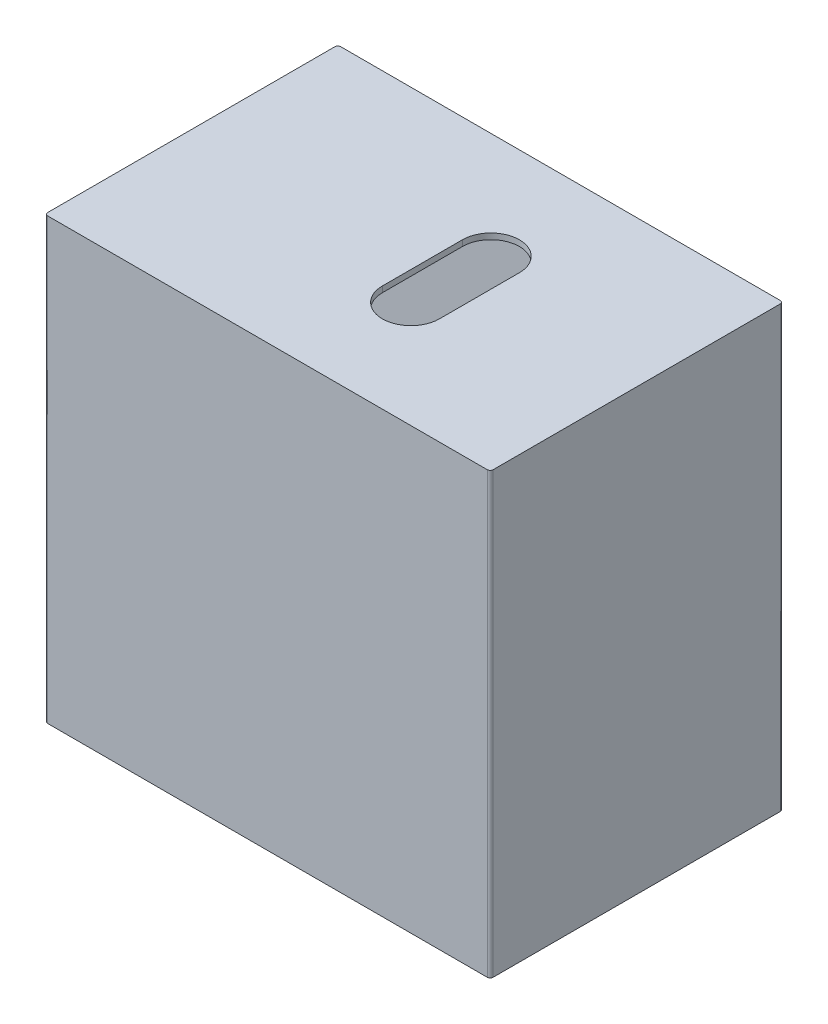
SolidWorks part; units mm, degrees
ref_plane "Front Plane" through (0, 0, 0) normal (0, 0, 1) x (1, 0, 0)
ref_plane "Top Plane" through (0, 0, 0) normal (0, 1, 0) x (1, 0, 0)
ref_plane "Right Plane" through (0, 0, 0) normal (1, 0, 0) x (0, 0, -1)
sketch "Sketch2" plane through (0, 0, 0) normal (0, 1, 0) x (1, 0, 0)
  line L0 (-14.8771, 11.2147) -> (17.0379, 11.2147)
  line L1 (17.0379, 11.2147) -> (17.0379, -11.4999)
  line L6 (17.0379, -11.4999) -> (-14.8548, -11.4999)
  line L7 (-19.8771, -6.4775) -> (-19.8771, 6.2147)
  line L8 (-29.1062, -20.0603) -> (-29.1062, 19.9397)
  line L9 (-75.1292, -50.0603) -> (74.8708, -50.0603)
  line L10 (-75.1292, 49.9397) -> (74.8708, 49.9397)
  line L11 (75.8708, 48.9397) -> (75.8708, -49.0603)
  line L12 (-29.1062, 19.9397) -> (-76.1292, 19.9397)
  line L13 (-29.1062, -20.0603) -> (-76.1292, -20.0603)
  line L14 (-76.1292, 48.9397) -> (-76.1292, 19.9397)
  line L15 (-76.1292, -20.0603) -> (-76.1292, -49.0603)
  line L16 (-76.1292, 19.9397) -> (-76.1292, -20.0603)
  line L17 (-76.1292, 17.9397) -> (-76.1292, -18.0603)
  line L18 (-31.1062, 17.9397) -> (-76.1292, 17.9397)
  line L19 (-31.1062, 17.9397) -> (-31.1062, -18.0603)
  line L20 (-31.1062, -18.0603) -> (-76.1292, -18.0603)
  line L21 (-76.1292, 17.9397) -> (-76.1292, -18.0603)
  line L22 (-76.1292, 19.9397) -> (-76.1292, 17.9397)
  arc A2 (-14.8771, 11.2147) -> (-19.8771, 6.2147) centre (-14.8771, 6.2147) ccw
  arc A3 (-14.8548, -11.4999) -> (-19.8771, -6.4775) centre (-14.8548, -6.4775) cw
  arc A6 (-76.1292, 48.9397) -> (-75.1292, 49.9397) centre (-75.1292, 48.9397) cw
  arc A7 (-75.1292, -50.0603) -> (-76.1292, -49.0603) centre (-75.1292, -49.0603) cw
  circle A10 centre (-73.1292, 46.9397) radius 2
  circle A11 centre (72.8708, 46.9397) radius 2
  arc A12 (74.8708, -50.0603) -> (75.8708, -49.0603) centre (74.8708, -49.0603) ccw
  arc A13 (74.8708, 49.9397) -> (75.8708, 48.9397) centre (74.8708, 48.9397) cw
  circle A14 centre (72.8708, -47.0603) radius 2
  circle A15 centre (-73.1292, -47.0603) radius 2
  point P9 (-1.1292, -0.0603)
  dimension "D14" = 29
  dimension "D5" = 2
  dimension "D1" = 5
  dimension "D2" = 5.0223
  dimension "D3" = 1
  dimension "D6" = 1
  dimension "D4" = 2
  dimension "D7" = 2
  dimension "D8" = 2
  dimension "D9" = 2
  dimension "D10" = 2
  dimension "D11" = 2
  dimension "D12" = 2
  dimension "D15" = 29
  dimension "D17" = 36
extrude "Boss-Extrude7" add sketch "Sketch2" along normal blind 150 contours A13 L10 A6 L14 L12 L8 L13 L15 A7 L9 A12 L11 A15 A14 A11 A10 L6 A3 L7 A2 L0 L1 | A3 L6 L1 L0 A2 L7 | A10 | L20 L19 L18 L16 | L19 L20 L16 L13 L8 L12 L18 | A15 | A14 | A11 region at (-1.1938, 0, 0.142) region at (-52.6177, 0, 19.443) region at (-27.2867, 0, 0.0603) region at (-53.6177, 0, 0.0603) region at (-73.1292, 0, -46.9397) region at (72.8708, 0, 47.0603) region at (-73.1292, 0, 47.0603)
extrude "Cut-Extrude8" cut sketch "Sketch2<42>" along normal blind 3 contours A15 | A14 | A11 | A10
sketch "Sketch2<42>" plane through (0, 0, 0) normal (0, 1, 0) x (1, 0, 0) same geometry as "Sketch2"
shell "Shell4" thickness 2 removed face at (-73.1292, 0, -44.9397)
extrude "Boss-Extrude8" add sketch "Sketch2<43>" along normal blind 36 contours L19 L20 L16 L13 L8 L12 L18 | L20 L19 L18 L16 region at (-52.6177, 0, 19.443) region at (-53.6177, 0, 0.0603)
sketch "Sketch2<43>" plane through (0, 0, 0) normal (0, 1, 0) x (1, 0, 0) same geometry as "Sketch2"
extrude "Cut-Extrude9" cut sketch "Sketch2<44>" along normal blind 33 contours L20 L19 L18 L16 region at (-53.6177, 0, 0.0603)
sketch "Sketch2<44>" plane through (0, 0, 0) normal (0, 1, 0) x (1, 0, 0) same geometry as "Sketch2"
sketch "Sketch7" plane through (0, 33, 0) normal (0, -1, 0) x (1, 0, 0)
  line L0 (-42.0071, -8.7067) -> (-42.0071, 8.7067) construction
  line L1 (-49.3854, -8.7067) -> (-49.3854, 8.7067)
  line L2 (-34.6289, -8.7067) -> (-34.6289, 8.7067)
  arc A0 (-49.3854, -8.7067) -> (-34.6289, -8.7067) centre (-42.0071, -8.7067) ccw
  arc A1 (-34.6289, 8.7067) -> (-49.3854, 8.7067) centre (-42.0071, 8.7067) ccw
  point P2 (-42.0071, 0)
extrude "Cut-Extrude11" cut sketch "Sketch7" against normal blind 33
fillet "Fillet4" radius 1 1 edges at (-76.1292, 33, 0.0603)
sketch "Sketch8" plane through (0, 150, 0) normal (0, 1, 0) x (1, 0, 0)
  line L3 (12.41, -13.6466) -> (12.41, 13.6466) construction
  line L4 (2.6801, -13.6466) -> (2.6801, 13.6466)
  line L5 (22.1398, -13.6466) -> (22.1398, 13.6466)
  arc A2 (2.6801, -13.6466) -> (22.1398, -13.6466) centre (12.41, -13.6466) ccw
  arc A3 (22.1398, 13.6466) -> (2.6801, 13.6466) centre (12.41, 13.6466) ccw
  point P8 (12.41, 0)
extrude "Boss-Extrude11" add sketch "Sketch8" against normal blind 40
extrude "Cut-Extrude16" cut sketch "Sketch8<7>" against normal blind 40
sketch "Sketch8<7>" plane through (0, 150, 0) normal (0, 1, 0) x (1, 0, 0) same geometry as "Sketch8"
